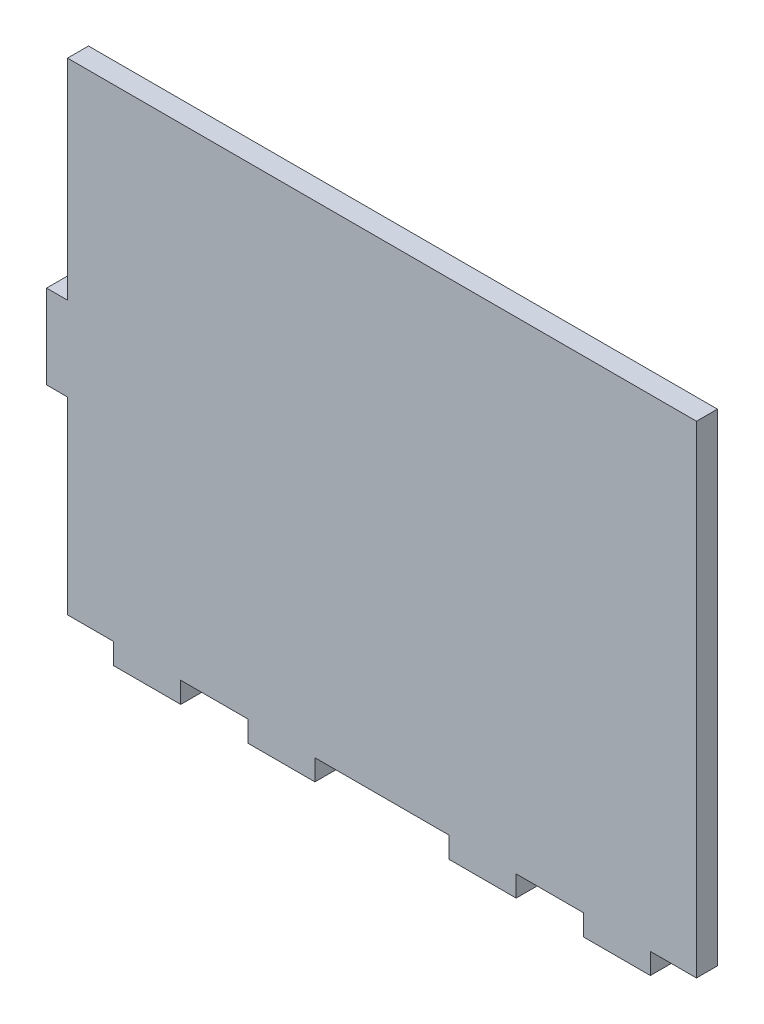
SolidWorks part; units mm, degrees
material "Beech"
ref_plane "Front" through (0, 0, 0) normal (0, 0, 1) x (1, 0, 0)
ref_plane "Top" through (0, 0, 0) normal (0, 1, 0) x (1, 0, 0)
ref_plane "Right" through (0, 0, 0) normal (1, 0, 0) x (0, 0, -1)
sketch "Sketch1" plane through (0, 0, 0) normal (0, 0, 1) x (1, 0, 0)
  line L0 (-40, 28.75) -> (0, 28.75) construction
  line L1 (0, 0) -> (-40, 0) construction
  line L2 (0, 0) -> (0, 33.75) construction
  line L3 (0, 33.75) -> (-40, 33.75) construction
  line L4 (-40, 0) -> (-40, 33.75) construction
  line L5 (0, 0) -> (-40, 33.75) construction
  line L6 (0, 33.75) -> (-40, 0) construction
  line L7 (-40, -28.75) -> (-40, 28.75) construction
  line L8 (-40, 28.75) -> (-32, 28.75) construction
  line L17 (-8, -28.75) -> (8, -28.75)
  line L18 (-8, -31.25) -> (-8, -28.75)
  line L19 (-16, -31.25) -> (-8, -31.25)
  line L20 (-16, -28.75) -> (-16, -31.25)
  line L21 (-24, -28.75) -> (-16, -28.75)
  line L22 (-24, -31.25) -> (-24, -28.75)
  line L23 (-32, -31.25) -> (-24, -31.25)
  line L24 (-32, -28.75) -> (-32, -31.25)
  line L25 (-40, -28.75) -> (-32, -28.75)
  line L26 (8, -31.25) -> (8, -28.75)
  line L27 (16, -31.25) -> (8, -31.25)
  line L28 (16, -28.75) -> (16, -31.25)
  line L29 (24, -28.75) -> (16, -28.75)
  line L30 (24, -31.25) -> (24, -28.75)
  line L31 (32, -31.25) -> (24, -31.25)
  line L32 (32, -28.75) -> (32, -31.25)
  line L33 (40, -28.75) -> (32, -28.75)
  line L34 (40, -28.75) -> (40, 28.75) construction
  line L35 (40, 28.75) -> (32, 28.75) construction
  line L36 (40, 28.75) -> (-40, 28.75)
  line L37 (-37.5, -28.75) -> (-37.5, 28.75) construction
  line L40 (-37.5, -6.25) -> (-40, -6.25)
  line L42 (-40, 3.75) -> (-37.5, 3.75)
  line L48 (-37.5, 28.75) -> (-37.5, 3.75)
  line L49 (-40, 3.75) -> (-40, -6.25)
  line L50 (-37.5, -6.25) -> (-37.5, -28.75)
  line L51 (37.5, -28.75) -> (37.5, 28.75)
  point P4 (-20, 16.875)
  point P28 (0, -28.75)
  dimension "D1" = 5
  dimension "D2" = 33.75
  dimension "D3" = 40
  dimension "D4" = 2.5
  dimension "D5" = 2.5
  dimension "D6" = 10
  dimension "D7" = 25
extrude "Boss-Extrude1" add sketch "Sketch1" along normal blind 2.5 contours L33 L51 L36 L48 L42 L49 L40 L50 L25 L24 L23 L22 L21 L20 L19 L18 L17 L26 L27 L28 L29 L30 L31 L32 region at (-0.2193, -0.5504, 0)
sketch "Sketch2" plane through (0, 0, 0) normal (0, 0, 1) x (1, 0, 0)
  line L0 (-33.7768, -20.25) -> (-8.7768, -20.25) construction
  line L1 (-33.7768, -23.75) -> (-8.7768, -23.75) construction
  line L2 (-8, -28.75) -> (8, -28.75) construction
  text T0 "OPPOSITE\r\n" font "Century Gothic" height 3.5
  text T1 "Made In Egypt" font "Century Gothic" height 2
  dimension "D1" = 3.5
  dimension "D2" = 5
  dimension "D4" = 25
extrude "Cut-Extrude1" cut sketch "Sketch2" along normal blind 1
